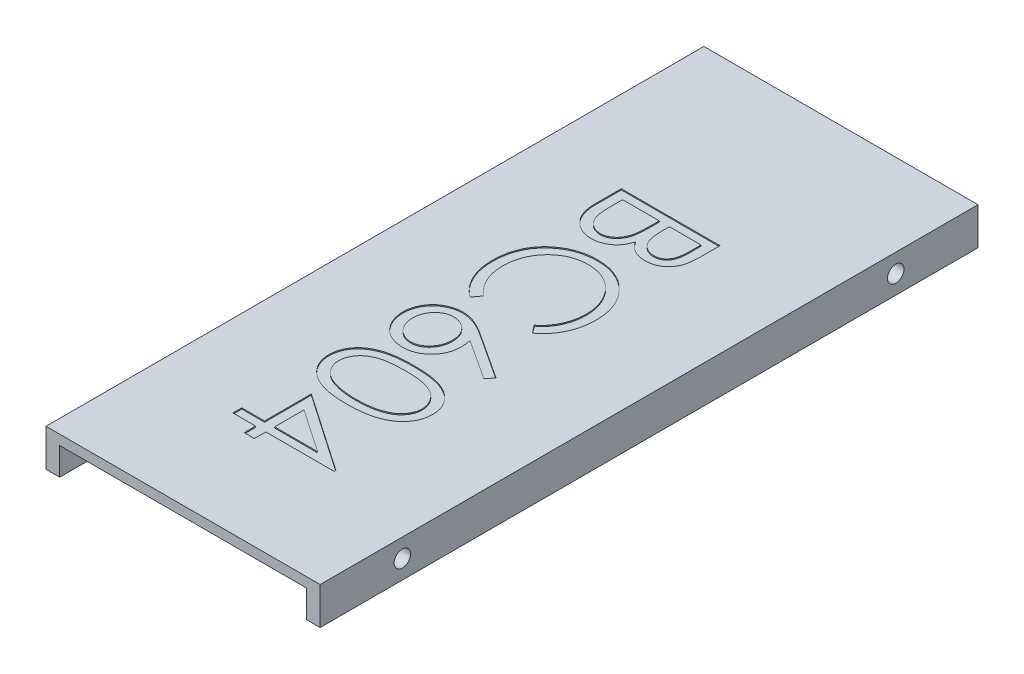
SolidWorks part; units mm, degrees
ref_plane "Front Plane" through (0, 0, 0) normal (0, 0, 1) x (1, 0, 0)
ref_plane "Top Plane" through (0, 0, 0) normal (0, 1, 0) x (1, 0, 0)
ref_plane "Right Plane" through (0, 0, 0) normal (1, 0, 0) x (0, 0, -1)
sketch "Sketch2" plane through (0, 0, 0) normal (0, 0, 1) x (1, 0, 0)
  line L1 (-251.2821, 174.5411) -> (248.7179, 174.5411)
  line L2 (-251.2821, 174.5411) -> (-251.2821, 156.5411)
  line L3 (-226.2821, 156.5411) -> (223.7179, 156.5411)
  line L4 (248.7179, 174.5411) -> (248.7179, 156.5411)
  line L6 (-251.2821, 156.5411) -> (-251.2821, 106.5411)
  line L7 (-251.2821, 106.5411) -> (-226.2821, 106.5411)
  line L8 (-226.2821, 156.5411) -> (-226.2821, 106.5411)
  line L10 (248.7179, 156.5411) -> (248.7179, 106.5411)
  line L11 (248.7179, 106.5411) -> (223.7179, 106.5411)
  line L12 (223.7179, 156.5411) -> (223.7179, 106.5411)
  dimension "D1" = 500
  dimension "D2" = 18
  dimension "D3" = 25
  dimension "D4" = 50
  dimension "D5" = 25
  dimension "D6" = 50
extrude "Boss-Extrude1" add sketch "Sketch2" along normal blind 1200 contours L3 L12 L11 L10 L4 L1 L2 L6 L7 L8
sketch "Sketch4" plane through (0, 0, 0) normal (1, 0, 0) x (0, 0, -1)
  line L0 (-600, 174.5411) -> (-600, 106.5411)
  line L2 (-1200, 174.5411) -> (0, 174.5411) construction
  line L3 (-1200, 106.5411) -> (0, 106.5411) construction
  circle A0 centre (-1050, 140.5411) radius 15
  circle A1 centre (-150, 140.5411) radius 15
  dimension "D1" = 30
extrude "Cut-Extrude1" cut sketch "Sketch4" against normal through all both and the other way through all contours A0
extrude "Cut-Extrude2" cut sketch "Sketch4<3>" against normal through all and the other way through all contours A1
sketch "Sketch4<3>" plane through (0, 0, 0) normal (1, 0, 0) x (0, 0, -1) same geometry as "Sketch4"
sketch "Sketch9" plane through (0, 174.5411, 0) normal (0, 1, 0) x (1, 0, 0)
  line L0 (-101.8538, -276.968) -> (-101.8538, -1001.968)
  line L1 (-94.5452, -1001.968) -> (-94.5452, -276.968)
  line L2 (-94.5452, -276.968) -> (-94.5452, -1001.968)
sketch "Sketch10" plane through (0, 174.5411, 0) normal (0, 1, 0) x (1, 0, 0)
  text T0 "BC604" font "Century Gothic" height 180
extrude "Cut-Extrude3" cut sketch "Sketch10" against normal blind 2
sketch "Sketch12" plane through (0, 156.5411, 0) normal (0, -1, 0) x (-1, 0, 0)
  text T0 "BC604" font "Century Gothic" height 180
extrude "Cut-Extrude4" cut sketch "Sketch12" against normal blind 2
